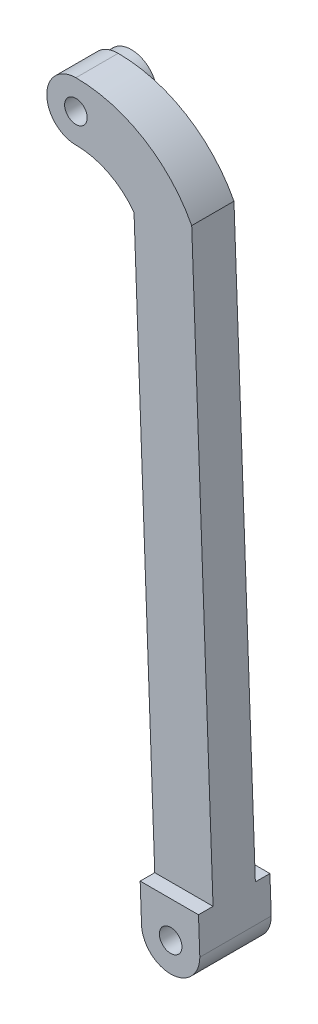
SolidWorks part; units mm, degrees
ref_plane "Plan de face" through (0, 0, 0) normal (0, 0, 1) x (1, 0, 0)
ref_plane "Plan de dessus" through (0, 0, 0) normal (0, 1, 0) x (1, 0, 0)
ref_plane "Plan de droite" through (0, 0, 0) normal (1, 0, 0) x (0, 0, -1)
sketch "Esquisse1" plane through (0, 0, 0) normal (0, 0, 1) x (1, 0, 0)
  line L2 (0, 0) -> (0, 90) construction
  line L3 (-15, 90) -> (0, 90) construction
  line L7 (-4, 0) -> (-7.0253, 81.98)
  line L8 (4, 0) -> (0.8864, 84.3712)
  circle A14 centre (0, 0) radius 1.55
  circle A15 centre (-15, 90) radius 1.55
  arc A16 (-4, 0) -> (4, 0) centre (0, 0) ccw
  arc A17 (-15, 94) -> (-15, 86) centre (-15, 90) ccw
  arc A18 (-15, 94) -> (0.8864, 84.3712) centre (-15, 76.0802) cw
  arc A19 (-7.0253, 81.98) -> (-15, 86) centre (-15, 76.0802) ccw
  dimension "D1" = 3.1
  dimension "D2" = 3.1
  dimension "D3" = 90
  dimension "D5" = 8
  dimension "D6" = 8
  dimension "D4" = 15
extrude "Boss.-Extru.1" add sketch "Esquisse1" along normal blind 4.9 and the other way blind 4.9 contours A19 L7 A16 L8 A18 A17 A15 A14 region at (-2.7634, 48.2405, 0)
sketch "Esquisse3" plane through (0, 0, 4.9) normal (0, 0, 1) x (1, 0, 0)
  line L0 (-7.0253, 81.98) -> (-6.4982, 67.6966)
  line L1 (-4, 0) -> (-7.0253, 81.98) construction
  line L2 (-6.4982, 67.6966) -> (1.5018, 67.6966)
  line L3 (4, 0) -> (0.8864, 84.3712) construction
  line L4 (1.5018, 67.6966) -> (0.8864, 84.3712)
  arc A0 (-15, 86) -> (-15, 94) centre (-15, 90) cw
  arc A1 (-15, 94) -> (0.8864, 84.3712) centre (-15, 76.0802) cw
  arc A2 (-15, 86) -> (-7.0253, 81.98) centre (-15, 76.0802) cw
extrude "Enlèv. mat.-Extru.2" [suppressed] cut sketch "Esquisse3" against normal blind 3
sketch "Sketch1" plane through (0, 0, 4.9) normal (0, 0, 1) x (1, 0, 0)
  line L0 (-7.0253, 81.98) -> (-4.1828, 4.9536)
  line L1 (-4, 0) -> (-7.0253, 81.98) construction
  line L2 (0.8864, 84.3712) -> (3.8172, 4.9536)
  line L3 (4, 0) -> (0.8864, 84.3712) construction
  line L4 (-4.1828, 4.9536) -> (3.8172, 4.9536)
  arc A0 (0.8864, 84.3712) -> (-15, 94) centre (-15, 76.0802) ccw
  arc A1 (0.8864, 84.3712) -> (-15, 94) centre (-15, 76.0802) ccw construction
  arc A2 (-7.0253, 81.98) -> (-15, 86) centre (-15, 76.0802) ccw
  arc A3 (-7.0253, 81.98) -> (-15, 86) centre (-15, 76.0802) ccw construction
  arc A5 (-15, 94) -> (-15, 86) centre (-15, 90) ccw
extrude "Cut-Extrude1" cut sketch "Sketch1" against normal blind 2
mirror "Mirror1" about plane through (0, 0, 0) normal (0, 0, 1) of "Cut-Extrude1"
sketch "Sketch2" plane through (0, 0, -2.9) normal (0, 0, -1) x (-1, 0, 0)
  circle A0 centre (15, 90) radius 1.55
  circle A1 centre (15, 90) radius 3.55
  dimension "D1" = 2
extrude "Boss-Extrude1" add sketch "Sketch2" along normal blind 1.8
